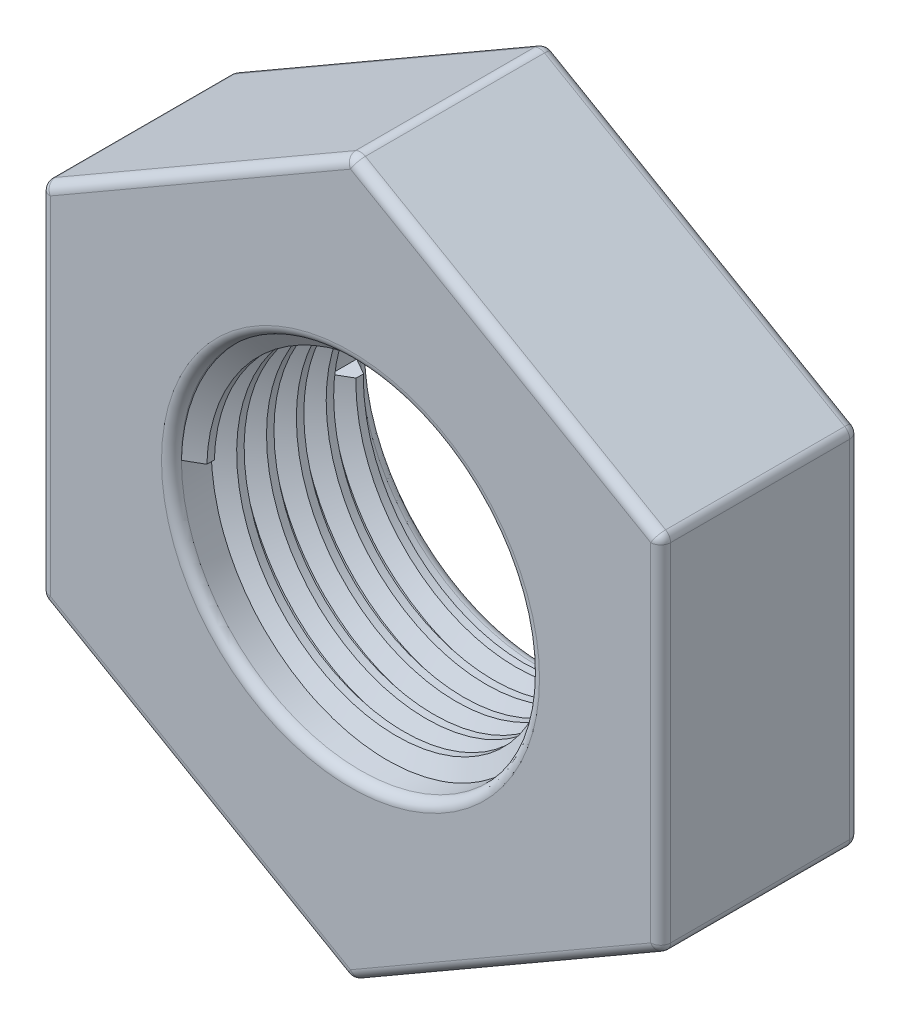
SolidWorks part; units mm, degrees
material "AISI 4140 Steel, quenched & tempered"
ref_plane "Front Plane" through (0, 0, 0) normal (1, 0, 0) x (0, 1, 0)
ref_plane "Top Plane" through (0, 0, 0) normal (0, 0, 1) x (0, 1, 0)
ref_plane "Right Plane" through (0, 0, 0) normal (0, 1, 0) x (-1, 0, 0)
sketch "Sketch1" plane through (0, 0, 0) normal (0, 0, 1) x (0, 1, 0)
  line L1 (-18, 0) -> (-9, -15.5885)
  line L2 (-9, -15.5885) -> (9, -15.5885)
  line L3 (9, -15.5885) -> (18, 0)
  line L4 (18, 0) -> (9, 15.5885)
  line L5 (9, 15.5885) -> (-9, 15.5885)
  line L6 (-9, 15.5885) -> (-18, 0)
  circle A0 centre (0, 0) radius 18 construction
  circle A1 centre (0, 0) radius 9
  point P11 (0, 15.5885)
  dimension "D2" = 18
  dimension "D1" = 18
extrude "Boss-Extrude1" add sketch "Sketch1" along normal blind 10
fillet "Fillet1" radius 0.5 20 edges at (9, 0, 0) (9, 0, 10) (-7.7942, -13.5, 0) (7.7942, -13.5, 0) (15.5885, 0, 0) (7.7942, 13.5, 0) (-7.7942, 13.5, 0) (-15.5885, 0, 0) (-7.7942, -13.5, 10) (7.7942, -13.5, 10) (15.5885, 0, 10) (-7.7942, 13.5, 10) (-15.5885, 0, 10) (-15.5885, -9, 5) (-15.5885, 9, 5) (0, 18, 5) (15.5885, 9, 5) (15.5885, -9, 5) (0, -18, 5) (7.7942, 13.5, 10)
thread "Thread2" pitch 1.5 method extrude profile "Thread Profile2" start angle 0, offset 0, length 0, pitch 1.5, diameter 18
ref_plane "Plane2" through (-9, 0, 9.5) normal (0, -1, 0) x (-1, 0, 0)
sketch "Thread Profile2" plane through (-9, 0, 9.5) normal (0, -1, 0) x (-1, 0, 0)
  line L0 (0, 0) -> (0, 1.5) construction
  line L11 (0, 0) -> (0, 1.3125)
  line L12 (0, 1.3125) -> (-0.8119, 0.8437)
  line L13 (-0.8119, 0.8437) -> (-0.8119, 0.4687)
  line L15 (-0.8119, 0.4687) -> (0, 0)
  line L17 (-0.8119, 0.6562) -> (0, 0.6562) construction
  point P2 (0, 0)
  dimension "Pitch" = 1.5
  dimension "Profile_Angle" = 60
  dimension "Profile_Land" = 0.375
  dimension "Profile_Height" = 0.8119
ref_axis "Axis1" through (0, 0, -0.5) along (0, 0, 1)
